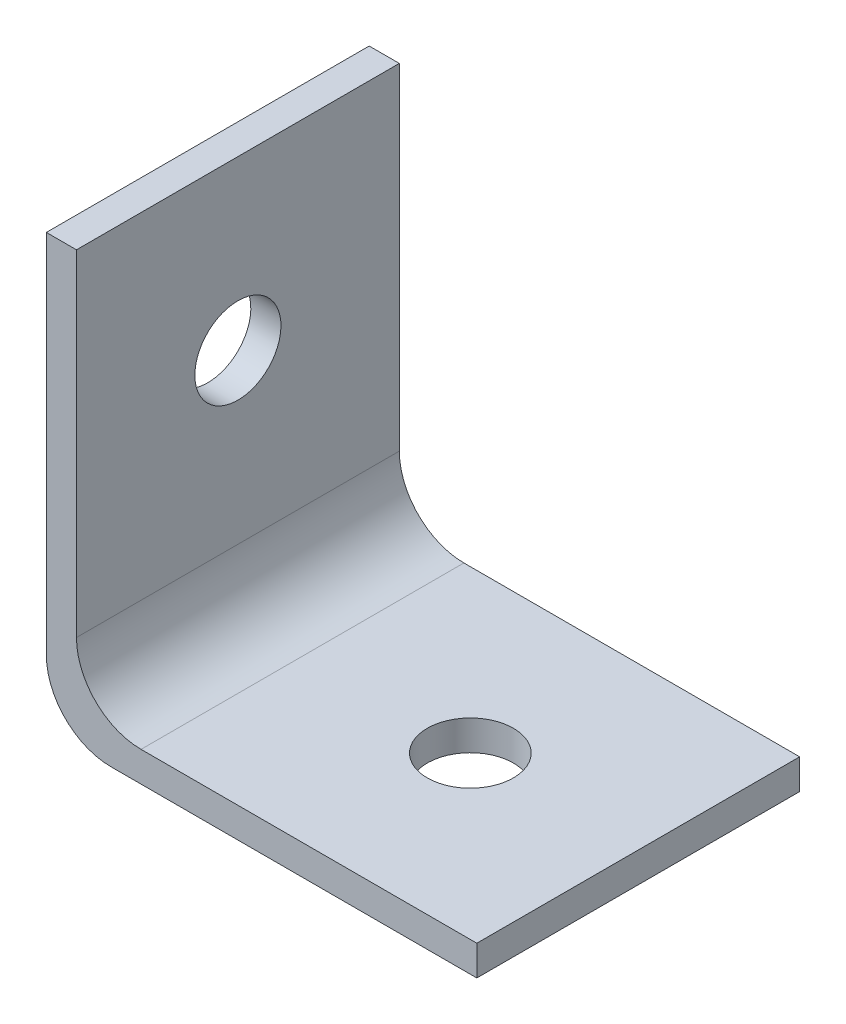
SolidWorks part; units mm, degrees
ref_plane "Front Plane" through (0, 0, 0) normal (0, 0, 1) x (1, 0, 0)
ref_plane "Top Plane" through (0, 0, 0) normal (0, 1, 0) x (1, 0, 0)
ref_plane "Right Plane" through (0, 0, 0) normal (1, 0, 0) x (0, 0, -1)
sketch "Sketch1" plane through (0, 0, 0) normal (0, 0, 1) x (1, 0, 0)
  line L0 (0, 3) -> (0, 20)
  line L1 (0, 20) -> (1.4, 20)
  line L2 (1.4, 20) -> (1.4, 4.4)
  line L3 (4.4, 1.4) -> (20, 1.4)
  line L4 (20, 1.4) -> (20, 0)
  line L5 (20, 0) -> (3, 0)
  arc A0 (1.4, 4.4) -> (4.4, 1.4) centre (4.4, 4.4) ccw
  arc A1 (0, 3) -> (3, 0) centre (3, 3) ccw
  point P5 (0, 0)
  point P12 (0, 0)
  dimension "D3" = 3
  dimension "D1" = 20
  dimension "D2" = 1.4
extrude "Boss-Extrude1" add sketch "Sketch1" along normal blind 15
sketch "Sketch2" plane through (0, 1.4, 0) normal (0, 1, 0) x (1, 0, 0)
  line L0 (20, 0) -> (4.4, 0) construction
  line L1 (20, -15) -> (20, 0) construction
  circle A0 centre (12.2, -7.5) radius 2
  point P4 (12.2, 0)
  point P7 (20, -7.5)
  dimension "D1" = 4
extrude "Cut-Extrude1" cut sketch "Sketch2" against normal through all
sketch "Sketch3" plane through (1.4, 0, 0) normal (1, 0, 0) x (0, 0, -1)
  line L0 (-15, 20) -> (0, 20) construction
  line L1 (0, 4.4) -> (0, 20) construction
  circle A0 centre (-7.5, 12.2) radius 2
  point P4 (-7.5, 20)
  point P7 (0, 12.2)
  dimension "D1" = 4
extrude "Cut-Extrude2" cut sketch "Sketch3" against normal through all
